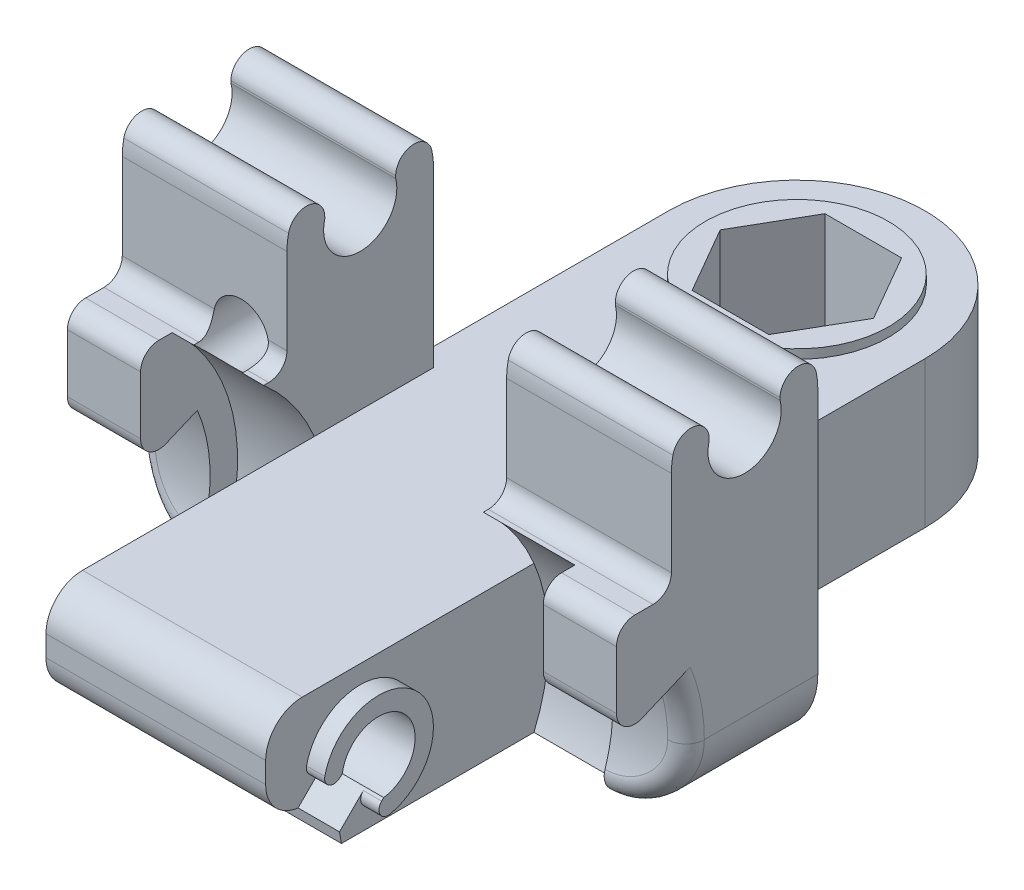
SolidWorks part; units mm, degrees
ref_plane "Front Plane" through (0, 0, 0) normal (0, 0, 1) x (1, 0, 0)
ref_plane "Top Plane" through (0, 0, 0) normal (0, 1, 0) x (1, 0, 0)
ref_plane "Right Plane" through (0, 0, 0) normal (1, 0, 0) x (0, 0, -1)
sketch "Sketch3" plane through (0, 0, 0) normal (1, 0, 0) x (0, 0, -1)
  line L0 (0.2828, -1.9799) -> (-1.9799, 0.2828)
  line L1 (0.2828, -1.9799) -> (-1.1314, -3.3941)
  line L2 (-1.1314, -3.3941) -> (-0.8188, -5.1668)
  line L3 (-0.8188, -5.1668) -> (-4.7772, -9.1252)
  line L4 (-1.9799, 0.2828) -> (-3.3941, -1.1314)
  line L5 (-3.3941, -1.1314) -> (-5.1668, -0.8188)
  line L6 (-5.1668, -0.8188) -> (-9.1252, -4.7772)
  line L7 (-0.8485, -0.8485) -> (0, 0) construction
  line L8 (0, 0) -> (-2, 0) construction
  line L9 (-1.9799, 0.2828) -> (-5.1668, -0.8188) construction
  line L10 (-0.8188, -5.1668) -> (0.2828, -1.9799) construction
  circle A0 centre (0, 0) radius 2
  circle A1 centre (0, 0) radius 9.8 construction
  circle A2 centre (0, 0) radius 10.3 construction
  circle A3 centre (0, 0) radius 10.3
  dimension "D1" = 4
  dimension "D2" = 19.6
  dimension "D4" = 0.5
  dimension "D5" = 2
  dimension "D7" = 3.2
  dimension "D6" = 1.8
  dimension "D8" = 45
  dimension "D9" = 125
extrude "Boss-Extrude1" add sketch "Sketch3" along normal mid plane 12 contours A3 L6 L5 L4 A0 L1 L2 L3 | A3 region at (0, -1.5013, -1.731)
sketch "Sketch5" plane through (0, 0, 0) normal (1, 0, 0) x (0, 0, -1)
  line L0 (0, 10.3) -> (29.856, 10.3)
  line L1 (29.856, 10.3) -> (29.856, -10.3)
  line L2 (29.856, -10.3) -> (0, -10.3)
  arc A0 (-4.7772, -9.1252) -> (-9.1252, -4.7772) centre (0, 0) ccw construction
  arc A1 (0, -10.3) -> (0, 10.3) centre (0, 0) ccw
  dimension "D1" = 29.856
extrude "Boss-Extrude2" add sketch "Sketch5" along normal mid plane 14
sketch "Sketch6" plane through (0, 10.3, 0) normal (0, 1, 0) x (1, 0, 0)
  line L0 (7, 29.856) -> (-7, 29.856) construction
  circle A0 centre (0, 29.856) radius 7
extrude "Boss-Extrude3" add sketch "Sketch6" against normal up to surface (20.6 mm away) up to face at (0, -10.3, -9.952)
sketch "Sketch7" plane through (0, 0, 0) normal (0, 1, 0) x (1, 0, 0)
  circle A0 centre (0, 29.856) radius 4.5
  dimension "D1" = 9
extrude "Boss-Extrude4" add sketch "Sketch7" along normal blind 8 and the other way blind 8
sketch "Sketch8" plane through (0, 10.3, 0) normal (0, 1, 0) x (1, 0, 0)
  line L0 (6, -10.3) -> (6, 0) construction
  line L1 (-6, 0) -> (-6, -10.3) construction
  line L3 (7, 0) -> (7, 29.856) construction
  line L4 (-7, 29.856) -> (-7, 0) construction
  line L5 (-7, 0) -> (-6, 0) construction
  line L6 (6, 0) -> (7, 0) construction
  line L7 (6, -10.3) -> (6, 0)
  line L8 (-6, 0) -> (-6, -10.3)
  line L9 (-6, -10.3) -> (6, -10.3)
  line L10 (7, 0) -> (7, 29.856)
  line L11 (-7, 29.856) -> (-7, 0)
  line L12 (-7, 0) -> (-6, 0)
  line L13 (6, 0) -> (7, 0)
  arc A0 (7, 29.856) -> (-7, 29.856) centre (0, 29.856) ccw construction
  arc A1 (7, 29.856) -> (-7, 29.856) centre (0, 29.856) ccw
  line M10 (7, 0) -> (7, 29.856)
  arc M11 (7, 29.856) -> (-7, 29.856) centre (0, 29.856) ccw
  line M12 (-7, 29.856) -> (-7, 0)
  line M13 (-7, 0) -> (-6, 0)
  line M14 (-6, 0) -> (6, 0)
  line M15 (6, 0) -> (7, 0)
extrude "Cut-Extrude2" cut sketch "Sketch8" against normal offset from surface (6.3 mm away) 4 contours M15 M10 M11 M12 M13 M14 | L8 L9 L7 M14 region at (0, 10.3, 5.15) region at (0, 10.3, -17.7114) up to plane "Top Plane"
sketch "Sketch9" plane through (0, -10.3, 0) normal (0, -1, 0) x (1, 0, 0)
  line L7 (6, 0) -> (6, 10.3)
  line L8 (7, 0) -> (6, 0)
  line L9 (7, -29.856) -> (7, 0)
  line L10 (-7, 0) -> (-7, -29.856)
  line L11 (-6, 0) -> (-7, 0)
  line L12 (-6, 10.3) -> (-6, 0)
  line L13 (6, 10.3) -> (-6, 10.3)
  line L14 (6, 0) -> (6, 10.3)
  line L15 (7, 0) -> (6, 0)
  line L16 (7, -29.856) -> (7, 0)
  line L17 (-7, 0) -> (-7, -29.856)
  line L18 (-6, 0) -> (-7, 0)
  line L19 (-6, 10.3) -> (-6, 0)
  line L20 (6, 10.3) -> (-6, 10.3)
  arc A1 (-7, -29.856) -> (7, -29.856) centre (0, -29.856) ccw
  arc A2 (-7, -29.856) -> (7, -29.856) centre (0, -29.856) ccw
  line M10 (-7, 0) -> (-7, -29.856)
  arc M11 (-7, -29.856) -> (7, -29.856) centre (0, -29.856) ccw
  line M12 (7, -29.856) -> (7, 0)
  line M13 (7, 0) -> (6, 0)
  line M14 (6, 0) -> (-6, 0)
  line M15 (-6, 0) -> (-7, 0)
  dimension "D1" = 0
extrude "Cut-Extrude4" cut sketch "Sketch9" against normal offset from surface (6.3 mm away) 4 contours M15 M10 M11 M12 M13 M14 | L14 L20 L19 M14 region at (0, -10.3, 5.15) region at (0, -10.3, -17.7114) up to plane "Top Plane"
sketch "Sketch24" plane through (-6, 0, 0) normal (-1, 0, 0) x (0, 0, 1)
  line L0 (1.9799, 0.2828) -> (2.9258, -0.6631)
  line L1 (1.9799, 0.2828) -> (3.3941, -1.1314) construction
  line L2 (-0.2828, -1.9799) -> (0.6631, -2.9258)
  line L3 (-0.2828, -1.9799) -> (1.1314, -3.3941) construction
  arc A0 (1.9799, 0.2828) -> (-0.2828, -1.9799) centre (0, 0) ccw construction
  arc A1 (1.9799, 0.2828) -> (-0.2828, -1.9799) centre (0, 0) ccw
  circle A2 centre (0, 0) radius 3
  line M5 (1.1314, -3.3941) -> (-0.2828, -1.9799)
  arc M6 (-0.2828, -1.9799) -> (1.9799, 0.2828) centre (0, 0) cw
  line M7 (1.9799, 0.2828) -> (3.3941, -1.1314)
  dimension "D1" = 6
extrude "Boss-Extrude6" add sketch "Sketch24" along normal blind 1 contours A2 M7 M5 M6 region at (-6, 1.4742, -1.4742)
fillet "Fillet3" radius 0.5 2 edges at (-6.5, -2.9258, 0.6631) (-6.5, -0.6631, 2.9258)
mirror "Mirror1" about plane through (0, 0, 0) normal (1, 0, 0) of "Fillet3", "Boss-Extrude6"
sketch "Sketch10" plane through (0, 0, 0) normal (1, 0, 0) x (0, 0, -1)
  line L3 (9.4916, -4) -> (29.856, -4)
  line L4 (29.856, -4) -> (29.856, 4)
  line L5 (29.856, 4) -> (9.4916, 4)
  line L10 (8, 7.8) -> (8, 17.5) construction
  line L11 (8, 17.5) -> (16, 17.5) construction
  line L12 (16, 17.5) -> (16, 4) construction
  line L13 (3.3109, 7.8) -> (8, 7.8)
  line L14 (0, 0) -> (4.0245, 9.4812) construction
  line L15 (4.0245, 9.4812) -> (3.3109, 7.8)
  line L16 (29.856, 4) -> (9.4916, 4) construction
  line L17 (16, 4) -> (9.4916, 4)
  line L18 (8, 13.5) -> (16, 13.5) construction
  line L19 (26, 14) -> (26, 4) construction
  line L20 (29.856, -4) -> (9.4916, -4) construction
  line L21 (10.0635, 14) -> (13.9365, 14) construction
  line L22 (13.9365, 14) -> (13.9365, 17)
  line L23 (10.0635, 17) -> (10.0635, 14)
  line L24 (8, 13.5) -> (8, 7.8)
  line L25 (16, 13.5) -> (16, 4)
  line L26 (16, -4) -> (9.4916, -4)
  line L27 (16, 4) -> (16, -4)
  arc A0 (10.0635, 14) -> (13.9365, 14) centre (12, 13.5) ccw
  arc A1 (9.4916, -4) -> (9.4916, 4) centre (0, 0) ccw
  arc A2 (9.4916, 4) -> (4.0245, 9.4812) centre (0, 0) ccw
  arc A3 (16, 13.5) -> (13.9365, 17) centre (12, 13.5) ccw
  arc A4 (10.0635, 17) -> (8, 13.5) centre (12, 13.5) ccw
  arc A5 (9.4916, -4) -> (9.4916, 4) centre (0, 0) ccw construction
  arc A6 (9.4916, -4) -> (9.4916, 4) centre (0, 0) ccw
  point P1 (4.0245, 9.4812)
  dimension "D8" = 4
  dimension "D9" = 2
  dimension "D10" = 2.5
  dimension "D2" = 67
  dimension "D3" = 10
  dimension "D4" = 13.5
  dimension "D5" = 9.7
  dimension "D6" = 12
  dimension "D7" = 7.8
  dimension "D1" = 0
extrude "Boss-Extrude5" add sketch "Sketch10" along normal mid plane 30 contours A6 L26 L27 L17 | L23 A4 L24 L13 L15 A2 L17 L25 A3 L22 A0 region at (0, 0, -13.0126) region at (0, 9.3226, -12.0467)
ref_plane "Plane1" through (6, 0, 0) normal (1, 0, 0) x (0, 0, -1)
ref_plane "Plane2" through (-6, 0, 0) normal (1, 0, 0) x (0, 0, -1)
sketch "Sketch13" plane through (-6, 0, 0) normal (1, 0, 0) x (0, 0, -1)
  line L0 (0, 5) -> (36.856, 5)
  line L2 (36.856, 4) -> (36.856, 5) construction
  circle A0 centre (0, 0) radius 5 construction
  dimension "D1" = 10
ref_plane "Plane3" through (0, 0, 0) normal (0, 0, 1) x (1, 0, 0)
ref_plane "Plane4" [suppressed] through (0, 0, -32.856) normal (0, 0, -1) x (-1, 0, 0)
ref_plane "Plane5" [suppressed] through (-3, 0, 0) normal (-1, 0, 0) x (0, 0, 1)
sketch "Sketch18" [suppressed] plane through (0, 0, -32.856) normal (0, 0, -1) x (-1, 0, 0)
  line L0 (0, 29) -> (0, 16) construction
  line L2 (3, 29) -> (-3, 29) construction
  circle A0 centre (0, 16) radius 1.9
  dimension "D2" = 3.8
  dimension "D1" = 13
extrude "Cut-Extrude5" [suppressed] cut sketch "Sketch18" against normal blind 1
sketch "Sketch20" plane through (0, 4, 0) normal (0, 1, 0) x (1, 0, 0)
  line L0 (0, 25.356) -> (0, 0) construction
  line L2 (-6, -16) -> (6, -16)
  line L3 (-6, -16) -> (-6, 16)
  line L4 (-6, 16) -> (6, 16)
  line L5 (6, -16) -> (6, 16)
  line L6 (-6, -16) -> (6, 16) construction
  line L7 (-6, 16) -> (6, -16) construction
  line L8 (-7, 16) -> (7, 16) construction
  dimension "D1" = 12
extrude "Cut-Extrude7" cut sketch "Sketch20" along normal through all
sketch "Sketch32" plane through (6, 0, 0) normal (1, 0, 0) x (0, 0, -1)
  line L0 (-5.1668, -0.8188) -> (-5.1668, 4)
  line L1 (9.4916, 4) -> (-9.4916, 4) construction
  line L9 (-3.3941, -1.1314) -> (-2.0905, 0.1722)
  line L10 (0.1722, -2.0905) -> (-1.1314, -3.3941)
  line L11 (-1.1314, -3.3941) -> (-1.0245, -4)
  line L12 (-1.0245, -4) -> (9.4916, -4)
  line L13 (9.4916, 4) -> (-9.4916, 4)
  line L14 (-8.348, -4) -> (-5.1668, -0.8188)
  line L15 (-5.1668, -0.8188) -> (-3.3941, -1.1314)
  line L16 (-3.3941, -1.1314) -> (-2.0905, 0.1722)
  line L17 (0.1722, -2.0905) -> (-1.1314, -3.3941)
  line L18 (-1.1314, -3.3941) -> (-1.0245, -4)
  line L19 (-1.0245, -4) -> (9.4916, -4)
  line L20 (9.4916, 4) -> (-9.4916, 4)
  line L21 (-8.348, -4) -> (-5.1668, -0.8188)
  line L22 (-5.1668, -0.8188) -> (-3.3941, -1.1314)
  line L24 (-9.4916, -4) -> (-8.348, -4)
  line L25 (-9.4916, -4) -> (-8.348, -4)
  arc A5 (-2.9329, 0.6309) -> (-2.0905, 0.1722) centre (-2.4441, 0.5258) ccw
  arc A6 (0.6309, -2.9329) -> (-2.9329, 0.6309) centre (0, 0) ccw
  arc A7 (0.1722, -2.0905) -> (0.6309, -2.9329) centre (0.5258, -2.4441) ccw
  arc A8 (9.4916, -4) -> (9.4916, 4) centre (0, 0) ccw
  arc A9 (-9.4916, 4) -> (-9.4916, -4) centre (0, 0) ccw
  arc A10 (-2.9329, 0.6309) -> (-2.0905, 0.1722) centre (-2.4441, 0.5258) ccw
  arc A11 (0.6309, -2.9329) -> (-2.9329, 0.6309) centre (0, 0) ccw
  arc A12 (0.1722, -2.0905) -> (0.6309, -2.9329) centre (0.5258, -2.4441) ccw
  arc A13 (9.4916, -4) -> (9.4916, 4) centre (0, 0) ccw
  arc A14 (-9.4916, 4) -> (-9.4916, -4) centre (0, 0) ccw
  line M21 (9.4916, 4) -> (-9.4916, 4)
  arc M22 (-9.4916, 4) -> (-9.4916, -4) centre (0, 0) ccw
  line M23 (-8.348, -4) -> (-5.1668, -0.8188)
  dimension "D1" = 0
extrude "Cut-Extrude9" cut sketch "Sketch32" against normal blind 25 contours L0 M23 M21 M22 region at (6, 0.439, 7.8127)
fillet "Fillet1" radius 2 2 edges at (0, 4, 5.1668) (0, -0.8188, 5.1668)
fillet "Fillet2" radius 1 4 edges at (-10.5, 17, -13.9365) (-10.5, 17, -10.0635) (10.5, 17, -10.0635) (10.5, 17, -13.9365)
sketch "Sketch23" plane through (0, 4, 0) normal (0, 1, 0) x (1, 0, 0)
  line L0 (-7, 29.856) -> (7, 29.856) construction
  line L1 (4.1881, 29.856) -> (2.094, 33.483)
  line L2 (2.094, 33.483) -> (-2.094, 33.483)
  line L3 (-2.094, 33.483) -> (-4.1881, 29.856)
  line L4 (-4.1881, 29.856) -> (-2.094, 26.229)
  line L5 (-2.094, 26.229) -> (2.094, 26.229)
  line L6 (2.094, 26.229) -> (4.1881, 29.856)
  line L7 (-7, 16) -> (-7, 29.856) construction
  circle A0 centre (0, 29.856) radius 3.627 construction
  dimension "D1" = 7.254
extrude "Cut-Extrude8" cut sketch "Sketch23" against normal through all
sketch "Sketch25" plane through (15, 0, 0) normal (1, 0, 0) x (0, 0, -1)
  line L0 (10.0635, 13) -> (13.9365, 13)
  arc A0 (10.0635, 14) -> (13.9365, 14) centre (12, 13.5) ccw construction
  arc A1 (10.0635, 14) -> (13.9365, 14) centre (12, 13.5) ccw
  arc M14 (13.9365, 14) -> (10.0635, 14) centre (12, 13.5) cw
  dimension "D1" = 1.5
extrude "Boss-Extrude7" [suppressed] add sketch "Sketch25" against normal blind 1 contours L0 M14
fillet "Fillet4" [suppressed] radius 0.5
mirror "Mirror2" [suppressed] about plane through (0, 0, 0) normal (1, 0, 0)
ref_plane "Plane6" through (-8.5, 0, 0) normal (-1, 0, 0) x (0, 0, 1)
sketch "Sketch27" plane through (-8.5, 0, 0) normal (-1, 0, 0) x (0, 0, 1)
  line L0 (0, 8.5) -> (-25.4214, 8.5)
  circle A0 centre (0, 0) radius 8.5 construction
  dimension "D1" = 17
sweep "Cut-Sweep1" cut path "Sketch27" circular profile diameter 3 parameters "D3"=3
sketch "Sketch28" plane through (15, 0, 0) normal (1, 0, 0) x (0, 0, -1)
  line L0 (0, 0) -> (9.4812, 4.0245) construction
  line L1 (9.4812, 4.0245) -> (5, 2.1224) construction
  line L2 (0, 0) -> (0, 8.2854) construction
  line L3 (6.7268, 7.8) -> (5, 7.8)
  line L4 (5, 7.8) -> (5, 2.1224)
  line L5 (8, 13.5) -> (8, 7.8) construction
  line L6 (9.4916, -4) -> (-1.0245, -4) construction
  line L7 (5, 2.1224) -> (8.1004, 3.4384)
  line L8 (7.8384, -4) -> (9.4916, -4)
  arc A0 (9.4916, -4) -> (6.7268, 7.8) centre (0, 0) ccw construction
  arc A1 (9.4916, -4) -> (6.7268, 7.8) centre (0, 0) ccw
  arc A2 (7.8384, -4) -> (8.1004, 3.4384) centre (0, 0) ccw
  arc A3 (8.7584, -0.8544) -> (5.7472, 6.6641) centre (0, 0) ccw construction
  arc A4 (10.2513, -1) -> (6.7268, 7.8) centre (0, 0) ccw construction
  point P1 (0, 0)
  point P13 (9.5116, -3.9521)
  arc M6 (6.7268, 7.8) -> (9.4916, -4) centre (0, 0) cw
  dimension "D2" = 3
  dimension "D3" = 1.5
  dimension "D1" = 67
extrude "Boss-Extrude8" add sketch "Sketch28" against normal blind 4 contours L1 M6 region at (15, 2.3202, -9.9025)
fillet "Fillet8" radius 1 1 edges at (13, 2.1224, -5)
mirror "Mirror3" about plane through (0, 0, 0) normal (1, 0, 0) of "Fillet8", "Boss-Extrude8"
sketch "Sketch33" plane through (0, 4, 0) normal (0, 1, 0) x (1, 0, 0)
  line L0 (4.1881, 29.856) -> (2.094, 33.483) construction
  line L1 (2.094, 26.229) -> (4.1881, 29.856) construction
  line L2 (-2.094, 26.229) -> (2.094, 26.229) construction
  line L3 (-4.1881, 29.856) -> (-2.094, 26.229) construction
  line L4 (-2.094, 33.483) -> (-4.1881, 29.856) construction
  line L5 (2.094, 33.483) -> (-2.094, 33.483) construction
  line L6 (4.1881, 29.856) -> (2.094, 33.483)
  line L7 (2.094, 26.229) -> (4.1881, 29.856)
  line L8 (-2.094, 26.229) -> (2.094, 26.229)
  line L9 (-4.1881, 29.856) -> (-2.094, 26.229)
  line L10 (-2.094, 33.483) -> (-4.1881, 29.856)
  line L11 (2.094, 33.483) -> (-2.094, 33.483)
  arc A0 (7, 29.856) -> (-7, 29.856) centre (0, 29.856) ccw construction
  arc A1 (7, 29.856) -> (-7, 29.856) centre (0, 29.856) ccw
  circle A2 centre (0, 29.856) radius 5
  line M8 (4.1881, 29.856) -> (2.094, 26.229)
  line M9 (2.094, 26.229) -> (-2.094, 26.229)
  line M10 (-2.094, 26.229) -> (-4.1881, 29.856)
  line M11 (-4.1881, 29.856) -> (-2.094, 33.483)
  line M12 (-2.094, 33.483) -> (2.094, 33.483)
  line M13 (2.094, 33.483) -> (4.1881, 29.856)
  dimension "D1" = 10
extrude "Boss-Extrude9" add sketch "Sketch33" along normal blind 0.5 contours A2 M13 M8 M9 M10 M11 M12 region at (-4.8586, 4, -29.856)
ref_plane "Plane7" through (0, 0, 0) normal (0, -1, 0) x (-1, 0, 0)
fillet "Fillet9" radius 1 5 edges at (10.5, 7.8, -8) (-6.5867, 7.8, -8) (-12.4133, 7.8, -8) (13, 7.8, -5) (-13, 7.8, -5)
fillet "Fillet10" radius 4 2 edges at (-15, -4, -11.9192) (15, -4, -11.9192)
fillet "Fillet11" radius 1 4 edges at (-15, 1.7544, -8.6233) (15, 1.7544, -8.6233) (-14.2287, -2.3612, -8.4773) (13.3454, -3.2402, -8.1817)
